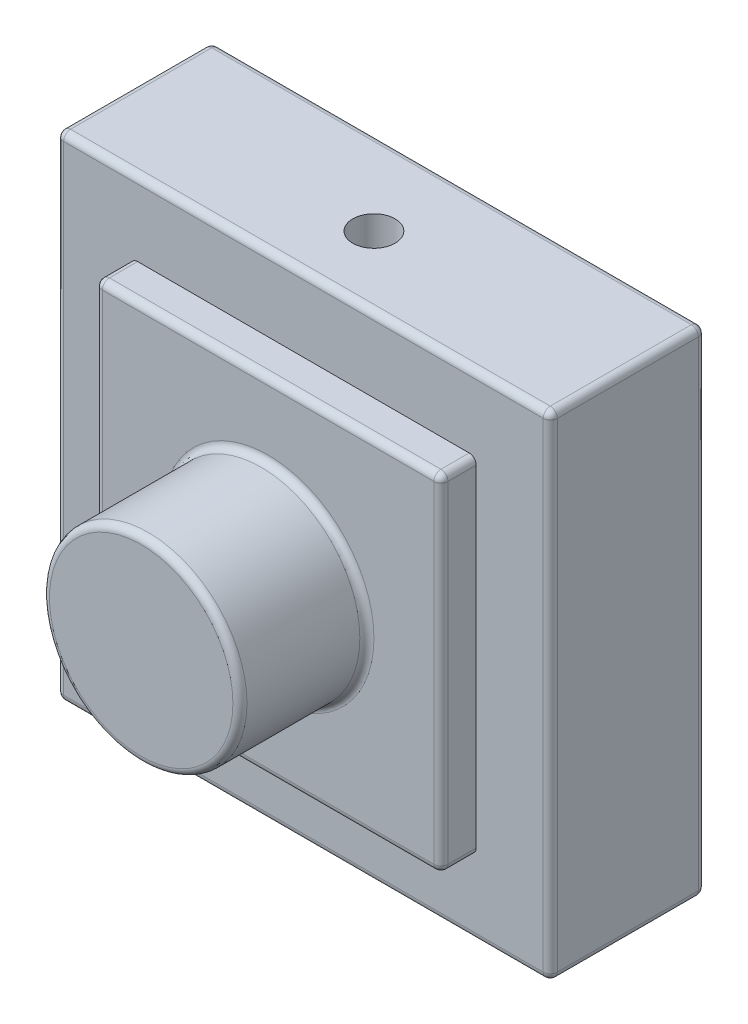
SolidWorks part; units mm, degrees
ref_plane "Front Plane" through (0, 0, 0) normal (0, 0, 1) x (1, 0, 0)
ref_plane "Top Plane" through (0, 0, 0) normal (0, 1, 0) x (1, 0, 0)
ref_plane "Right Plane" through (0, 0, 0) normal (1, 0, 0) x (0, 0, -1)
sketch "Sketch1" plane through (0, 0, 0) normal (0, 0, 1) x (1, 0, 0)
  line L1 (-17.5, 17.5) -> (17.5, 17.5)
  line L2 (-17.5, 17.5) -> (-17.5, -17.5)
  line L3 (-17.5, -17.5) -> (17.5, -17.5)
  line L4 (17.5, 17.5) -> (17.5, -17.5)
  line L5 (-17.5, 17.5) -> (17.5, -17.5) construction
  line L6 (-17.5, -17.5) -> (17.5, 17.5) construction
  point P0 (0, 0)
  dimension "D1" = 35
  dimension "D2" = 35
extrude "Boss-Extrude1" add sketch "Sketch1" along normal blind 11
sketch "Sketch2" plane through (0, 17.5, 0) normal (0, 1, 0) x (1, 0, 0)
  line L0 (0, 0) -> (0, -6) construction
  circle A0 centre (0, -6) radius 1.5
  dimension "D2" = 3
  dimension "D1" = 6
extrude "Cut-Extrude1" cut sketch "Sketch2" against normal blind 5
ref_plane "Plane4" through (0, 0, 0) normal (0, 1, 0) x (1, 0, 0)
mirror "Mirror1" about plane through (0, 0, 0) normal (0, 1, 0) of "Cut-Extrude1"
sketch "Sketch3" plane through (0, 0, 11) normal (0, 0, 1) x (1, 0, 0)
  line L1 (-12.25, 12.25) -> (12.25, 12.25)
  line L2 (-12.25, 12.25) -> (-12.25, -12.25)
  line L3 (-12.25, -12.25) -> (12.25, -12.25)
  line L4 (12.25, 12.25) -> (12.25, -12.25)
  line L5 (-12.25, 12.25) -> (12.25, -12.25) construction
  line L6 (-12.25, -12.25) -> (12.25, 12.25) construction
  point P0 (0, 0)
  dimension "D1" = 24.5
  dimension "D2" = 24.5
extrude "Boss-Extrude2" add sketch "Sketch3" along normal blind 2.5
sketch "Sketch4" plane through (0, 0, 13.5) normal (0, 0, 1) x (1, 0, 0)
  circle A0 centre (0, 0) radius 7
  dimension "D1" = 14
extrude "Boss-Extrude3" add sketch "Sketch4" along normal blind 9
fillet "Fillet1" radius 0.5 21 edges at (17.5, 0, 11) (17.5, 0, 0) (-17.5, 0, 0) (0, 17.5, 0) (0, -17.5, 0) (0, -17.5, 11) (-17.5, 0, 11) (0, 12.25, 13.5) (-12.25, 0, 13.5) (0, -12.25, 13.5) (12.25, 0, 13.5) (-12.25, -12.25, 12.25) (-12.25, 12.25, 12.25) (12.25, -12.25, 12.25) (7, 0, 13.5) (12.25, 12.25, 12.25) (-17.5, -17.5, 5.5) (-17.5, 17.5, 5.5) (17.5, -17.5, 5.5) (17.5, 17.5, 5.5) (0, 17.5, 11)
fillet "Fillet2" radius 0.5 1 edges at (7, 0, 22.5)
ref_plane "Plane5" through (0, 0, 22.5) normal (0, 0, 1) x (1, 0, 0)
ref_plane "Plane6" [suppressed] through (0, 0, 2022.5) normal (0, 0, 1) x (1, 0, 0)
sketch "Sketch5" [suppressed] plane through (0, 0, 0) normal (1, 0, 0) x (0, 0, -1)
  line L0 (-22.5, 0) -> (-2022.5, 0) construction
  line L1 (-22.5, 7.15) -> (-22.5, -7.15) construction
  line L2 (-22.5, 0) -> (-2022.5, -3464.1016) construction
  line L3 (-2022.5, -3464.1016) -> (-2022.5, 0) construction
  dimension "D1" = 60
  dimension "D2" = 2000
ref_plane "Plane7" [suppressed] through (0, 0, 2022.5) normal (0, 0, 1) x (1, 0, 0)
sketch "Sketch8" [suppressed] plane through (0, 0, 2022.5) normal (0, 0, 1) x (1, 0, 0)
  line L1 (-4839.2071, 3464.1016) -> (4839.2071, 3464.1016)
  line L2 (-4839.2071, 3464.1016) -> (-4839.2071, -3464.1016)
  line L3 (-4839.2071, -3464.1016) -> (4839.2071, -3464.1016)
  line L4 (4839.2071, 3464.1016) -> (4839.2071, -3464.1016)
  line L5 (-4839.2071, 3464.1016) -> (4839.2071, -3464.1016) construction
  line L6 (-4839.2071, -3464.1016) -> (4839.2071, 3464.1016) construction
  point P0 (0, 0)
  dimension "D1" = 9678.4142
sketch "Sketch9" plane through (0, 0, 0) normal (1, 0, 0) x (0, 0, -1)
  line L0 (-22.5, 0) -> (-54.0248, 0) construction
  line L1 (-22.5, 7.15) -> (-22.5, -7.15) construction
  line L2 (-22.5, 0) -> (-55.8883, 57.8303) construction
  line L3 (-22.5, 0) -> (-54.1365, -54.796) construction
  point P5 (-55.8883, 57.8303)
  point P8 (-54.0248, -54.796)
  dimension "D1" = 60
  dimension "D2" = 60
sketch "Sketch10" plane through (0, 0, 0) normal (0, 1, 0) x (1, 0, 0)
  line L0 (0, -22.5) -> (-51.5419, -52.2577) construction
  line L1 (0, -22.5) -> (0, -54.1365) construction
  line L2 (-7.15, -22.5) -> (7.15, -22.5) construction
  line L3 (0, -22.5) -> (58.55, -56.3038) construction
  point P6 (-51.5419, -52.2577)
  point P8 (58.55, -56.3038)
  dimension "D1" = 60
  dimension "D2" = 60
